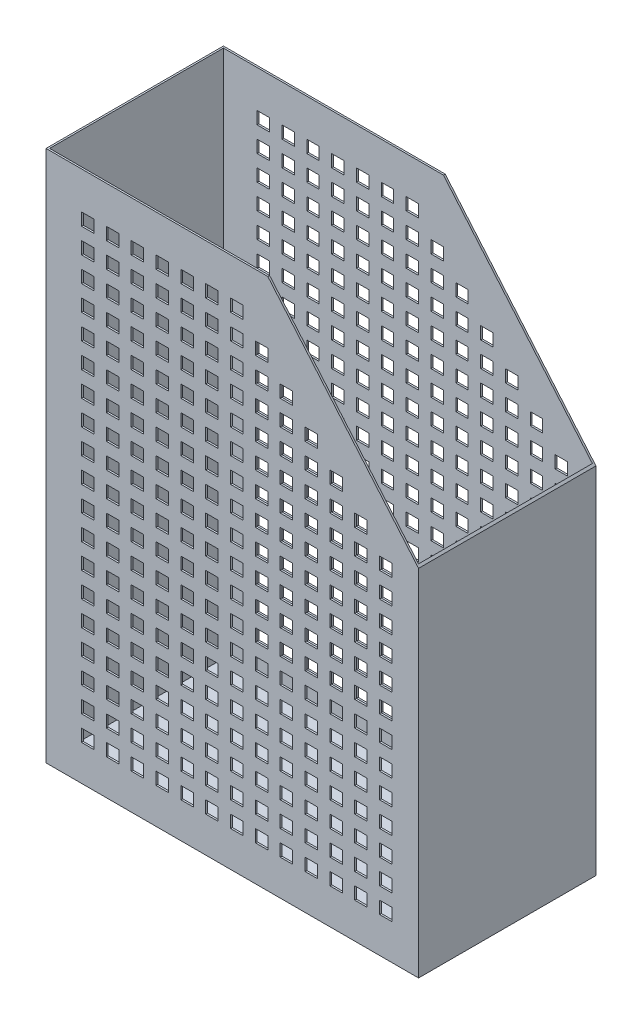
SolidWorks part; units mm, degrees
ref_plane "Front Plane" through (0, 0, 0) normal (0, 0, 1) x (1, 0, 0)
ref_plane "Top Plane" through (0, 0, 0) normal (0, 1, 0) x (1, 0, 0)
ref_plane "Right Plane" through (0, 0, 0) normal (1, 0, 0) x (0, 0, -1)
sketch "Sketch1" plane through (0, 0, 0) normal (0, 0, 1) x (1, 0, 0)
  line L0 (0, 0) -> (0, 300)
  line L1 (0, 300) -> (125, 300)
  line L2 (125, 300) -> (210, 200)
  line L3 (210, 200) -> (210, 0)
  line L4 (210, 0) -> (0, 0)
  dimension "D1" = 300
  dimension "D2" = 210
  dimension "D3" = 125
  dimension "D4" = 200
extrude "Boss-Extrude1" add sketch "Sketch1" along normal mid plane 100
shell "Shell1" thickness 1
sketch "Sketch2" plane through (0, 0, 50) normal (0, 0, 1) x (1, 0, 0)
  line L0 (0, 0) -> (210, 0) construction
  line L1 (20, 20) -> (27, 20)
  line L2 (20, 20) -> (20, 27)
  line L3 (20, 27) -> (27, 27)
  line L4 (27, 20) -> (27, 27)
  line L5 (34, 20) -> (34, 27)
  line L6 (34, 20) -> (41, 20)
  line L7 (41, 20) -> (41, 27)
  line L8 (34, 27) -> (41, 27)
  line L9 (48, 20) -> (48, 27)
  line L10 (0, 0) -> (210, 0)
  line L11 (210, 0) -> (210, 200)
  line L12 (210, 200) -> (125, 300)
  line L13 (125, 300) -> (0, 300)
  line L14 (0, 300) -> (0, 0)
  line L15 (0, 0) -> (210, 0)
  line L16 (210, 0) -> (210, 200)
  line L17 (210, 200) -> (125, 300)
  line L18 (125, 300) -> (0, 300)
  line L19 (0, 300) -> (0, 0)
  line L20 (48, 20) -> (55, 20)
  line L21 (55, 20) -> (55, 27)
  line L22 (48, 27) -> (55, 27)
  line L23 (62, 20) -> (62, 27)
  line L24 (62, 20) -> (69, 20)
  line L25 (69, 20) -> (69, 27)
  line L26 (62, 27) -> (69, 27)
  line L27 (76, 20) -> (76, 27)
  line L28 (76, 20) -> (83, 20)
  line L29 (83, 20) -> (83, 27)
  line L30 (76, 27) -> (83, 27)
  line L31 (90, 20) -> (90, 27)
  line L32 (90, 20) -> (97, 20)
  line L33 (97, 20) -> (97, 27)
  line L34 (90, 27) -> (97, 27)
  line L35 (104, 20) -> (104, 27)
  line L36 (104, 20) -> (111, 20)
  line L37 (111, 20) -> (111, 27)
  line L38 (104, 27) -> (111, 27)
  line L39 (118, 20) -> (118, 27)
  line L40 (118, 20) -> (125, 20)
  line L41 (125, 20) -> (125, 27)
  line L42 (118, 27) -> (125, 27)
  line L43 (132, 20) -> (132, 27)
  line L44 (132, 20) -> (139, 20)
  line L45 (139, 20) -> (139, 27)
  line L46 (132, 27) -> (139, 27)
  line L47 (146, 20) -> (146, 27)
  line L48 (146, 20) -> (153, 20)
  line L49 (153, 20) -> (153, 27)
  line L50 (146, 27) -> (153, 27)
  line L51 (160, 20) -> (160, 27)
  line L52 (160, 20) -> (167, 20)
  line L53 (167, 20) -> (167, 27)
  line L54 (160, 27) -> (167, 27)
  line L55 (174, 20) -> (174, 27)
  line L56 (174, 20) -> (181, 20)
  line L57 (181, 20) -> (181, 27)
  line L58 (174, 27) -> (181, 27)
  line L59 (188, 20) -> (188, 27)
  line L60 (188, 20) -> (195, 20)
  line L61 (195, 20) -> (195, 27)
  line L62 (188, 27) -> (195, 27)
  line L63 (34, 34) -> (34, 41)
  line L64 (34, 34) -> (41, 34)
  line L65 (41, 34) -> (41, 41)
  line L66 (34, 41) -> (41, 41)
  line L67 (48, 34) -> (48, 41)
  line L68 (48, 34) -> (55, 34)
  line L69 (55, 34) -> (55, 41)
  line L70 (48, 41) -> (55, 41)
  line L71 (62, 34) -> (62, 41)
  line L72 (62, 34) -> (69, 34)
  line L73 (69, 34) -> (69, 41)
  line L74 (62, 41) -> (69, 41)
  line L75 (76, 34) -> (76, 41)
  line L76 (76, 34) -> (83, 34)
  line L77 (83, 34) -> (83, 41)
  line L78 (76, 41) -> (83, 41)
  line L79 (90, 34) -> (90, 41)
  line L80 (90, 34) -> (97, 34)
  line L81 (97, 34) -> (97, 41)
  line L82 (90, 41) -> (97, 41)
  line L83 (104, 34) -> (104, 41)
  line L84 (104, 34) -> (111, 34)
  line L85 (111, 34) -> (111, 41)
  line L86 (104, 41) -> (111, 41)
  line L87 (118, 34) -> (118, 41)
  line L88 (118, 34) -> (125, 34)
  line L89 (125, 34) -> (125, 41)
  line L90 (118, 41) -> (125, 41)
  line L91 (132, 34) -> (132, 41)
  line L92 (132, 34) -> (139, 34)
  line L93 (139, 34) -> (139, 41)
  line L94 (132, 41) -> (139, 41)
  line L95 (146, 34) -> (146, 41)
  line L96 (146, 34) -> (153, 34)
  line L97 (153, 34) -> (153, 41)
  line L98 (146, 41) -> (153, 41)
  line L99 (160, 34) -> (160, 41)
  line L100 (160, 34) -> (167, 34)
  line L101 (167, 34) -> (167, 41)
  line L102 (160, 41) -> (167, 41)
  line L103 (174, 34) -> (174, 41)
  line L104 (174, 34) -> (181, 34)
  line L105 (181, 34) -> (181, 41)
  line L106 (174, 41) -> (181, 41)
  line L107 (188, 34) -> (188, 41)
  line L108 (188, 34) -> (195, 34)
  line L109 (195, 34) -> (195, 41)
  line L110 (188, 41) -> (195, 41)
  line L111 (34, 48) -> (34, 55)
  line L112 (34, 48) -> (41, 48)
  line L113 (41, 48) -> (41, 55)
  line L114 (34, 55) -> (41, 55)
  line L115 (48, 48) -> (48, 55)
  line L116 (48, 48) -> (55, 48)
  line L117 (55, 48) -> (55, 55)
  line L118 (48, 55) -> (55, 55)
  line L119 (62, 48) -> (62, 55)
  line L120 (62, 48) -> (69, 48)
  line L121 (69, 48) -> (69, 55)
  line L122 (62, 55) -> (69, 55)
  line L123 (76, 48) -> (76, 55)
  line L124 (76, 48) -> (83, 48)
  line L125 (83, 48) -> (83, 55)
  line L126 (76, 55) -> (83, 55)
  line L127 (90, 48) -> (90, 55)
  line L128 (90, 48) -> (97, 48)
  line L129 (97, 48) -> (97, 55)
  line L130 (90, 55) -> (97, 55)
  line L131 (104, 48) -> (104, 55)
  line L132 (104, 48) -> (111, 48)
  line L133 (111, 48) -> (111, 55)
  line L134 (104, 55) -> (111, 55)
  line L135 (118, 48) -> (118, 55)
  line L136 (118, 48) -> (125, 48)
  line L137 (125, 48) -> (125, 55)
  line L138 (118, 55) -> (125, 55)
  line L139 (132, 48) -> (132, 55)
  line L140 (132, 48) -> (139, 48)
  line L141 (139, 48) -> (139, 55)
  line L142 (132, 55) -> (139, 55)
  line L143 (146, 48) -> (146, 55)
  line L144 (146, 48) -> (153, 48)
  line L145 (153, 48) -> (153, 55)
  line L146 (146, 55) -> (153, 55)
  line L147 (160, 48) -> (160, 55)
  line L148 (160, 48) -> (167, 48)
  line L149 (167, 48) -> (167, 55)
  line L150 (160, 55) -> (167, 55)
  line L151 (174, 48) -> (174, 55)
  line L152 (174, 48) -> (181, 48)
  line L153 (181, 48) -> (181, 55)
  line L154 (174, 55) -> (181, 55)
  line L155 (188, 48) -> (188, 55)
  line L156 (188, 48) -> (195, 48)
  line L157 (195, 48) -> (195, 55)
  line L158 (188, 55) -> (195, 55)
  line L159 (34, 62) -> (34, 69)
  line L160 (34, 62) -> (41, 62)
  line L161 (41, 62) -> (41, 69)
  line L162 (34, 69) -> (41, 69)
  line L163 (48, 62) -> (48, 69)
  line L164 (48, 62) -> (55, 62)
  line L165 (55, 62) -> (55, 69)
  line L166 (48, 69) -> (55, 69)
  line L167 (62, 62) -> (62, 69)
  line L168 (62, 62) -> (69, 62)
  line L169 (69, 62) -> (69, 69)
  line L170 (62, 69) -> (69, 69)
  line L171 (76, 62) -> (76, 69)
  line L172 (76, 62) -> (83, 62)
  line L173 (83, 62) -> (83, 69)
  line L174 (76, 69) -> (83, 69)
  line L175 (90, 62) -> (90, 69)
  line L176 (90, 62) -> (97, 62)
  line L177 (97, 62) -> (97, 69)
  line L178 (90, 69) -> (97, 69)
  line L179 (104, 62) -> (104, 69)
  line L180 (104, 62) -> (111, 62)
  line L181 (111, 62) -> (111, 69)
  line L182 (104, 69) -> (111, 69)
  line L183 (118, 62) -> (118, 69)
  line L184 (118, 62) -> (125, 62)
  line L185 (125, 62) -> (125, 69)
  line L186 (118, 69) -> (125, 69)
  line L187 (132, 62) -> (132, 69)
  line L188 (132, 62) -> (139, 62)
  line L189 (139, 62) -> (139, 69)
  line L190 (132, 69) -> (139, 69)
  line L191 (146, 62) -> (146, 69)
  line L192 (146, 62) -> (153, 62)
  line L193 (153, 62) -> (153, 69)
  line L194 (146, 69) -> (153, 69)
  line L195 (160, 62) -> (160, 69)
  line L196 (160, 62) -> (167, 62)
  line L197 (167, 62) -> (167, 69)
  line L198 (160, 69) -> (167, 69)
  line L199 (174, 62) -> (174, 69)
  line L200 (174, 62) -> (181, 62)
  line L201 (181, 62) -> (181, 69)
  line L202 (174, 69) -> (181, 69)
  line L203 (188, 62) -> (188, 69)
  line L204 (188, 62) -> (195, 62)
  line L205 (195, 62) -> (195, 69)
  line L206 (188, 69) -> (195, 69)
  line L207 (34, 76) -> (34, 83)
  line L208 (34, 76) -> (41, 76)
  line L209 (41, 76) -> (41, 83)
  line L210 (34, 83) -> (41, 83)
  line L211 (48, 76) -> (48, 83)
  line L212 (48, 76) -> (55, 76)
  line L213 (55, 76) -> (55, 83)
  line L214 (48, 83) -> (55, 83)
  line L215 (62, 76) -> (62, 83)
  line L216 (62, 76) -> (69, 76)
  line L217 (69, 76) -> (69, 83)
  line L218 (62, 83) -> (69, 83)
  line L219 (76, 76) -> (76, 83)
  line L220 (76, 76) -> (83, 76)
  line L221 (83, 76) -> (83, 83)
  line L222 (76, 83) -> (83, 83)
  line L223 (90, 76) -> (90, 83)
  line L224 (90, 76) -> (97, 76)
  line L225 (97, 76) -> (97, 83)
  line L226 (90, 83) -> (97, 83)
  line L227 (104, 76) -> (104, 83)
  line L228 (104, 76) -> (111, 76)
  line L229 (111, 76) -> (111, 83)
  line L230 (104, 83) -> (111, 83)
  line L231 (118, 76) -> (118, 83)
  line L232 (118, 76) -> (125, 76)
  line L233 (125, 76) -> (125, 83)
  line L234 (118, 83) -> (125, 83)
  line L235 (132, 76) -> (132, 83)
  line L236 (132, 76) -> (139, 76)
  line L237 (139, 76) -> (139, 83)
  line L238 (132, 83) -> (139, 83)
  line L239 (146, 76) -> (146, 83)
  line L240 (146, 76) -> (153, 76)
  line L241 (153, 76) -> (153, 83)
  line L242 (146, 83) -> (153, 83)
  line L243 (160, 76) -> (160, 83)
  line L244 (160, 76) -> (167, 76)
  line L245 (167, 76) -> (167, 83)
  line L246 (160, 83) -> (167, 83)
  line L247 (174, 76) -> (174, 83)
  line L248 (174, 76) -> (181, 76)
  line L249 (181, 76) -> (181, 83)
  line L250 (174, 83) -> (181, 83)
  line L251 (188, 76) -> (188, 83)
  line L252 (188, 76) -> (195, 76)
  line L253 (195, 76) -> (195, 83)
  line L254 (188, 83) -> (195, 83)
  line L255 (34, 90) -> (34, 97)
  line L256 (34, 90) -> (41, 90)
  line L257 (41, 90) -> (41, 97)
  line L258 (34, 97) -> (41, 97)
  line L259 (48, 90) -> (48, 97)
  line L260 (48, 90) -> (55, 90)
  line L261 (55, 90) -> (55, 97)
  line L262 (48, 97) -> (55, 97)
  line L263 (62, 90) -> (62, 97)
  line L264 (62, 90) -> (69, 90)
  line L265 (69, 90) -> (69, 97)
  line L266 (62, 97) -> (69, 97)
  line L267 (76, 90) -> (76, 97)
  line L268 (76, 90) -> (83, 90)
  line L269 (83, 90) -> (83, 97)
  line L270 (76, 97) -> (83, 97)
  line L271 (90, 90) -> (90, 97)
  line L272 (90, 90) -> (97, 90)
  line L273 (97, 90) -> (97, 97)
  line L274 (90, 97) -> (97, 97)
  line L275 (104, 90) -> (104, 97)
  line L276 (104, 90) -> (111, 90)
  line L277 (111, 90) -> (111, 97)
  line L278 (104, 97) -> (111, 97)
  line L279 (118, 90) -> (118, 97)
  line L280 (118, 90) -> (125, 90)
  line L281 (125, 90) -> (125, 97)
  line L282 (118, 97) -> (125, 97)
  line L283 (132, 90) -> (132, 97)
  line L284 (132, 90) -> (139, 90)
  line L285 (139, 90) -> (139, 97)
  line L286 (132, 97) -> (139, 97)
  line L287 (146, 90) -> (146, 97)
  line L288 (146, 90) -> (153, 90)
  line L289 (153, 90) -> (153, 97)
  line L290 (146, 97) -> (153, 97)
  line L291 (160, 90) -> (160, 97)
  line L292 (160, 90) -> (167, 90)
  line L293 (167, 90) -> (167, 97)
  line L294 (160, 97) -> (167, 97)
  line L295 (174, 90) -> (174, 97)
  line L296 (174, 90) -> (181, 90)
  line L297 (181, 90) -> (181, 97)
  line L298 (174, 97) -> (181, 97)
  line L299 (188, 90) -> (188, 97)
  line L300 (188, 90) -> (195, 90)
  line L301 (195, 90) -> (195, 97)
  line L302 (188, 97) -> (195, 97)
  line L303 (34, 104) -> (34, 111)
  line L304 (34, 104) -> (41, 104)
  line L305 (41, 104) -> (41, 111)
  line L306 (34, 111) -> (41, 111)
  line L307 (48, 104) -> (48, 111)
  line L308 (48, 104) -> (55, 104)
  line L309 (55, 104) -> (55, 111)
  line L310 (48, 111) -> (55, 111)
  line L311 (62, 104) -> (62, 111)
  line L312 (62, 104) -> (69, 104)
  line L313 (69, 104) -> (69, 111)
  line L314 (62, 111) -> (69, 111)
  line L315 (76, 104) -> (76, 111)
  line L316 (76, 104) -> (83, 104)
  line L317 (83, 104) -> (83, 111)
  line L318 (76, 111) -> (83, 111)
  line L319 (90, 104) -> (90, 111)
  line L320 (90, 104) -> (97, 104)
  line L321 (97, 104) -> (97, 111)
  line L322 (90, 111) -> (97, 111)
  line L323 (104, 104) -> (104, 111)
  line L324 (104, 104) -> (111, 104)
  line L325 (111, 104) -> (111, 111)
  line L326 (104, 111) -> (111, 111)
  line L327 (118, 104) -> (118, 111)
  line L328 (118, 104) -> (125, 104)
  line L329 (125, 104) -> (125, 111)
  line L330 (118, 111) -> (125, 111)
  line L331 (132, 104) -> (132, 111)
  line L332 (132, 104) -> (139, 104)
  line L333 (139, 104) -> (139, 111)
  line L334 (132, 111) -> (139, 111)
  line L335 (146, 104) -> (146, 111)
  line L336 (146, 104) -> (153, 104)
  line L337 (153, 104) -> (153, 111)
  line L338 (146, 111) -> (153, 111)
  line L339 (160, 104) -> (160, 111)
  line L340 (160, 104) -> (167, 104)
  line L341 (167, 104) -> (167, 111)
  line L342 (160, 111) -> (167, 111)
  line L343 (174, 104) -> (174, 111)
  line L344 (174, 104) -> (181, 104)
  line L345 (181, 104) -> (181, 111)
  line L346 (174, 111) -> (181, 111)
  line L347 (188, 104) -> (188, 111)
  line L348 (188, 104) -> (195, 104)
  line L349 (195, 104) -> (195, 111)
  line L350 (188, 111) -> (195, 111)
  line L351 (34, 118) -> (34, 125)
  line L352 (34, 118) -> (41, 118)
  line L353 (41, 118) -> (41, 125)
  line L354 (34, 125) -> (41, 125)
  line L355 (48, 118) -> (48, 125)
  line L356 (48, 118) -> (55, 118)
  line L357 (55, 118) -> (55, 125)
  line L358 (48, 125) -> (55, 125)
  line L359 (62, 118) -> (62, 125)
  line L360 (62, 118) -> (69, 118)
  line L361 (69, 118) -> (69, 125)
  line L362 (62, 125) -> (69, 125)
  line L363 (76, 118) -> (76, 125)
  line L364 (76, 118) -> (83, 118)
  line L365 (83, 118) -> (83, 125)
  line L366 (76, 125) -> (83, 125)
  line L367 (90, 118) -> (90, 125)
  line L368 (90, 118) -> (97, 118)
  line L369 (97, 118) -> (97, 125)
  line L370 (90, 125) -> (97, 125)
  line L371 (104, 118) -> (104, 125)
  line L372 (104, 118) -> (111, 118)
  line L373 (111, 118) -> (111, 125)
  line L374 (104, 125) -> (111, 125)
  line L375 (118, 118) -> (118, 125)
  line L376 (118, 118) -> (125, 118)
  line L377 (125, 118) -> (125, 125)
  line L378 (118, 125) -> (125, 125)
  line L379 (132, 118) -> (132, 125)
  line L380 (132, 118) -> (139, 118)
  line L381 (139, 118) -> (139, 125)
  line L382 (132, 125) -> (139, 125)
  line L383 (146, 118) -> (146, 125)
  line L384 (146, 118) -> (153, 118)
  line L385 (153, 118) -> (153, 125)
  line L386 (146, 125) -> (153, 125)
  line L387 (160, 118) -> (160, 125)
  line L388 (160, 118) -> (167, 118)
  line L389 (167, 118) -> (167, 125)
  line L390 (160, 125) -> (167, 125)
  line L391 (174, 118) -> (174, 125)
  line L392 (174, 118) -> (181, 118)
  line L393 (181, 118) -> (181, 125)
  line L394 (174, 125) -> (181, 125)
  line L395 (188, 118) -> (188, 125)
  line L396 (188, 118) -> (195, 118)
  line L397 (195, 118) -> (195, 125)
  line L398 (188, 125) -> (195, 125)
  line L399 (34, 132) -> (34, 139)
  line L400 (34, 132) -> (41, 132)
  line L401 (41, 132) -> (41, 139)
  line L402 (34, 139) -> (41, 139)
  line L403 (48, 132) -> (48, 139)
  line L404 (48, 132) -> (55, 132)
  line L405 (55, 132) -> (55, 139)
  line L406 (48, 139) -> (55, 139)
  line L407 (62, 132) -> (62, 139)
  line L408 (62, 132) -> (69, 132)
  line L409 (69, 132) -> (69, 139)
  line L410 (62, 139) -> (69, 139)
  line L411 (76, 132) -> (76, 139)
  line L412 (76, 132) -> (83, 132)
  line L413 (83, 132) -> (83, 139)
  line L414 (76, 139) -> (83, 139)
  line L415 (90, 132) -> (90, 139)
  line L416 (90, 132) -> (97, 132)
  line L417 (97, 132) -> (97, 139)
  line L418 (90, 139) -> (97, 139)
  line L419 (104, 132) -> (104, 139)
  line L420 (104, 132) -> (111, 132)
  line L421 (111, 132) -> (111, 139)
  line L422 (104, 139) -> (111, 139)
  line L423 (118, 132) -> (118, 139)
  line L424 (118, 132) -> (125, 132)
  line L425 (125, 132) -> (125, 139)
  line L426 (118, 139) -> (125, 139)
  line L427 (132, 132) -> (132, 139)
  line L428 (132, 132) -> (139, 132)
  line L429 (139, 132) -> (139, 139)
  line L430 (132, 139) -> (139, 139)
  line L431 (146, 132) -> (146, 139)
  line L432 (146, 132) -> (153, 132)
  line L433 (153, 132) -> (153, 139)
  line L434 (146, 139) -> (153, 139)
  line L435 (160, 132) -> (160, 139)
  line L436 (160, 132) -> (167, 132)
  line L437 (167, 132) -> (167, 139)
  line L438 (160, 139) -> (167, 139)
  line L439 (174, 132) -> (174, 139)
  line L440 (174, 132) -> (181, 132)
  line L441 (181, 132) -> (181, 139)
  line L442 (174, 139) -> (181, 139)
  line L443 (188, 132) -> (188, 139)
  line L444 (188, 132) -> (195, 132)
  line L445 (195, 132) -> (195, 139)
  line L446 (188, 139) -> (195, 139)
  line L447 (34, 146) -> (34, 153)
  line L448 (34, 146) -> (41, 146)
  line L449 (41, 146) -> (41, 153)
  line L450 (34, 153) -> (41, 153)
  line L451 (48, 146) -> (48, 153)
  line L452 (48, 146) -> (55, 146)
  line L453 (55, 146) -> (55, 153)
  line L454 (48, 153) -> (55, 153)
  line L455 (62, 146) -> (62, 153)
  line L456 (62, 146) -> (69, 146)
  line L457 (69, 146) -> (69, 153)
  line L458 (62, 153) -> (69, 153)
  line L459 (76, 146) -> (76, 153)
  line L460 (76, 146) -> (83, 146)
  line L461 (83, 146) -> (83, 153)
  line L462 (76, 153) -> (83, 153)
  line L463 (90, 146) -> (90, 153)
  line L464 (90, 146) -> (97, 146)
  line L465 (97, 146) -> (97, 153)
  line L466 (90, 153) -> (97, 153)
  line L467 (104, 146) -> (104, 153)
  line L468 (104, 146) -> (111, 146)
  line L469 (111, 146) -> (111, 153)
  line L470 (104, 153) -> (111, 153)
  line L471 (118, 146) -> (118, 153)
  line L472 (118, 146) -> (125, 146)
  line L473 (125, 146) -> (125, 153)
  line L474 (118, 153) -> (125, 153)
  line L475 (132, 146) -> (132, 153)
  line L476 (132, 146) -> (139, 146)
  line L477 (139, 146) -> (139, 153)
  line L478 (132, 153) -> (139, 153)
  line L479 (146, 146) -> (146, 153)
  line L480 (146, 146) -> (153, 146)
  line L481 (153, 146) -> (153, 153)
  line L482 (146, 153) -> (153, 153)
  line L483 (160, 146) -> (160, 153)
  line L484 (160, 146) -> (167, 146)
  line L485 (167, 146) -> (167, 153)
  line L486 (160, 153) -> (167, 153)
  line L487 (174, 146) -> (174, 153)
  line L488 (174, 146) -> (181, 146)
  line L489 (181, 146) -> (181, 153)
  line L490 (174, 153) -> (181, 153)
  line L491 (188, 146) -> (188, 153)
  line L492 (188, 146) -> (195, 146)
  line L493 (195, 146) -> (195, 153)
  line L494 (188, 153) -> (195, 153)
  line L495 (34, 160) -> (34, 167)
  line L496 (34, 160) -> (41, 160)
  line L497 (41, 160) -> (41, 167)
  line L498 (34, 167) -> (41, 167)
  line L499 (48, 160) -> (48, 167)
  line L500 (48, 160) -> (55, 160)
  line L501 (55, 160) -> (55, 167)
  line L502 (48, 167) -> (55, 167)
  line L503 (62, 160) -> (62, 167)
  line L504 (62, 160) -> (69, 160)
  line L505 (69, 160) -> (69, 167)
  line L506 (62, 167) -> (69, 167)
  line L507 (76, 160) -> (76, 167)
  line L508 (76, 160) -> (83, 160)
  line L509 (83, 160) -> (83, 167)
  line L510 (76, 167) -> (83, 167)
  line L511 (90, 160) -> (90, 167)
  line L512 (90, 160) -> (97, 160)
  line L513 (97, 160) -> (97, 167)
  line L514 (90, 167) -> (97, 167)
  line L515 (104, 160) -> (104, 167)
  line L516 (104, 160) -> (111, 160)
  line L517 (111, 160) -> (111, 167)
  line L518 (104, 167) -> (111, 167)
  line L519 (118, 160) -> (118, 167)
  line L520 (118, 160) -> (125, 160)
  line L521 (125, 160) -> (125, 167)
  line L522 (118, 167) -> (125, 167)
  line L523 (132, 160) -> (132, 167)
  line L524 (132, 160) -> (139, 160)
  line L525 (139, 160) -> (139, 167)
  line L526 (132, 167) -> (139, 167)
  line L527 (146, 160) -> (146, 167)
  line L528 (146, 160) -> (153, 160)
  line L529 (153, 160) -> (153, 167)
  line L530 (146, 167) -> (153, 167)
  line L531 (160, 160) -> (160, 167)
  line L532 (160, 160) -> (167, 160)
  line L533 (167, 160) -> (167, 167)
  line L534 (160, 167) -> (167, 167)
  line L535 (174, 160) -> (174, 167)
  line L536 (174, 160) -> (181, 160)
  line L537 (181, 160) -> (181, 167)
  line L538 (174, 167) -> (181, 167)
  line L539 (188, 160) -> (188, 167)
  line L540 (188, 160) -> (195, 160)
  line L541 (195, 160) -> (195, 167)
  line L542 (188, 167) -> (195, 167)
  line L543 (34, 174) -> (34, 181)
  line L544 (34, 174) -> (41, 174)
  line L545 (41, 174) -> (41, 181)
  line L546 (34, 181) -> (41, 181)
  line L547 (48, 174) -> (48, 181)
  line L548 (48, 174) -> (55, 174)
  line L549 (55, 174) -> (55, 181)
  line L550 (48, 181) -> (55, 181)
  line L551 (62, 174) -> (62, 181)
  line L552 (62, 174) -> (69, 174)
  line L553 (69, 174) -> (69, 181)
  line L554 (62, 181) -> (69, 181)
  line L555 (76, 174) -> (76, 181)
  line L556 (76, 174) -> (83, 174)
  line L557 (83, 174) -> (83, 181)
  line L558 (76, 181) -> (83, 181)
  line L559 (90, 174) -> (90, 181)
  line L560 (90, 174) -> (97, 174)
  line L561 (97, 174) -> (97, 181)
  line L562 (90, 181) -> (97, 181)
  line L563 (104, 174) -> (104, 181)
  line L564 (104, 174) -> (111, 174)
  line L565 (111, 174) -> (111, 181)
  line L566 (104, 181) -> (111, 181)
  line L567 (118, 174) -> (118, 181)
  line L568 (118, 174) -> (125, 174)
  line L569 (125, 174) -> (125, 181)
  line L570 (118, 181) -> (125, 181)
  line L571 (132, 174) -> (132, 181)
  line L572 (132, 174) -> (139, 174)
  line L573 (139, 174) -> (139, 181)
  line L574 (132, 181) -> (139, 181)
  line L575 (146, 174) -> (146, 181)
  line L576 (146, 174) -> (153, 174)
  line L577 (153, 174) -> (153, 181)
  line L578 (146, 181) -> (153, 181)
  line L579 (160, 174) -> (160, 181)
  line L580 (160, 174) -> (167, 174)
  line L581 (167, 174) -> (167, 181)
  line L582 (160, 181) -> (167, 181)
  line L583 (174, 174) -> (174, 181)
  line L584 (174, 174) -> (181, 174)
  line L585 (181, 174) -> (181, 181)
  line L586 (174, 181) -> (181, 181)
  line L587 (188, 174) -> (188, 181)
  line L588 (188, 174) -> (195, 174)
  line L589 (195, 174) -> (195, 181)
  line L590 (188, 181) -> (195, 181)
  line L591 (34, 188) -> (34, 195)
  line L592 (34, 188) -> (41, 188)
  line L593 (41, 188) -> (41, 195)
  line L594 (34, 195) -> (41, 195)
  line L595 (48, 188) -> (48, 195)
  line L596 (48, 188) -> (55, 188)
  line L597 (55, 188) -> (55, 195)
  line L598 (48, 195) -> (55, 195)
  line L599 (62, 188) -> (62, 195)
  line L600 (62, 188) -> (69, 188)
  line L601 (69, 188) -> (69, 195)
  line L602 (62, 195) -> (69, 195)
  line L603 (76, 188) -> (76, 195)
  line L604 (76, 188) -> (83, 188)
  line L605 (83, 188) -> (83, 195)
  line L606 (76, 195) -> (83, 195)
  line L607 (90, 188) -> (90, 195)
  line L608 (90, 188) -> (97, 188)
  line L609 (97, 188) -> (97, 195)
  line L610 (90, 195) -> (97, 195)
  line L611 (104, 188) -> (104, 195)
  line L612 (104, 188) -> (111, 188)
  line L613 (111, 188) -> (111, 195)
  line L614 (104, 195) -> (111, 195)
  line L615 (118, 188) -> (118, 195)
  line L616 (118, 188) -> (125, 188)
  line L617 (125, 188) -> (125, 195)
  line L618 (118, 195) -> (125, 195)
  line L619 (132, 188) -> (132, 195)
  line L620 (132, 188) -> (139, 188)
  line L621 (139, 188) -> (139, 195)
  line L622 (132, 195) -> (139, 195)
  line L623 (146, 188) -> (146, 195)
  line L624 (146, 188) -> (153, 188)
  line L625 (153, 188) -> (153, 195)
  line L626 (146, 195) -> (153, 195)
  line L627 (160, 188) -> (160, 195)
  line L628 (160, 188) -> (167, 188)
  line L629 (167, 188) -> (167, 195)
  line L630 (160, 195) -> (167, 195)
  line L631 (174, 188) -> (174, 195)
  line L632 (174, 188) -> (181, 188)
  line L633 (181, 188) -> (181, 195)
  line L634 (174, 195) -> (181, 195)
  line L635 (188, 188) -> (188, 195)
  line L636 (188, 188) -> (195, 188)
  line L637 (195, 188) -> (195, 195)
  line L638 (188, 195) -> (195, 195)
  line L639 (34, 202) -> (34, 209)
  line L640 (34, 202) -> (41, 202)
  line L641 (41, 202) -> (41, 209)
  line L642 (34, 209) -> (41, 209)
  line L643 (48, 202) -> (48, 209)
  line L644 (48, 202) -> (55, 202)
  line L645 (55, 202) -> (55, 209)
  line L646 (48, 209) -> (55, 209)
  line L647 (62, 202) -> (62, 209)
  line L648 (62, 202) -> (69, 202)
  line L649 (69, 202) -> (69, 209)
  line L650 (62, 209) -> (69, 209)
  line L651 (76, 202) -> (76, 209)
  line L652 (76, 202) -> (83, 202)
  line L653 (83, 202) -> (83, 209)
  line L654 (76, 209) -> (83, 209)
  line L655 (90, 202) -> (90, 209)
  line L656 (90, 202) -> (97, 202)
  line L657 (97, 202) -> (97, 209)
  line L658 (90, 209) -> (97, 209)
  line L659 (104, 202) -> (104, 209)
  line L660 (104, 202) -> (111, 202)
  line L661 (111, 202) -> (111, 209)
  line L662 (104, 209) -> (111, 209)
  line L663 (118, 202) -> (118, 209)
  line L664 (118, 202) -> (125, 202)
  line L665 (125, 202) -> (125, 209)
  line L666 (118, 209) -> (125, 209)
  line L667 (132, 202) -> (132, 209)
  line L668 (132, 202) -> (139, 202)
  line L669 (139, 202) -> (139, 209)
  line L670 (132, 209) -> (139, 209)
  line L671 (146, 202) -> (146, 209)
  line L672 (146, 202) -> (153, 202)
  line L673 (153, 202) -> (153, 209)
  line L674 (146, 209) -> (153, 209)
  line L675 (160, 202) -> (160, 209)
  line L676 (160, 202) -> (167, 202)
  line L677 (167, 202) -> (167, 209)
  line L678 (160, 209) -> (167, 209)
  line L679 (174, 202) -> (174, 209)
  line L680 (174, 202) -> (181, 202)
  line L681 (181, 202) -> (181, 209)
  line L682 (174, 209) -> (181, 209)
  line L683 (188, 202) -> (188, 209) [skipped]
  line L684 (188, 202) -> (195, 202) [skipped]
  line L685 (195, 202) -> (195, 209) [skipped]
  line L686 (188, 209) -> (195, 209) [skipped]
  line L687 (34, 216) -> (34, 223)
  line L688 (34, 216) -> (41, 216)
  line L689 (41, 216) -> (41, 223)
  line L690 (34, 223) -> (41, 223)
  line L691 (48, 216) -> (48, 223)
  line L692 (48, 216) -> (55, 216)
  line L693 (55, 216) -> (55, 223)
  line L694 (48, 223) -> (55, 223)
  line L695 (62, 216) -> (62, 223)
  line L696 (62, 216) -> (69, 216)
  line L697 (69, 216) -> (69, 223)
  line L698 (62, 223) -> (69, 223)
  line L699 (76, 216) -> (76, 223)
  line L700 (76, 216) -> (83, 216)
  line L701 (83, 216) -> (83, 223)
  line L702 (76, 223) -> (83, 223)
  line L703 (90, 216) -> (90, 223)
  line L704 (90, 216) -> (97, 216)
  line L705 (97, 216) -> (97, 223)
  line L706 (90, 223) -> (97, 223)
  line L707 (104, 216) -> (104, 223)
  line L708 (104, 216) -> (111, 216)
  line L709 (111, 216) -> (111, 223)
  line L710 (104, 223) -> (111, 223)
  line L711 (118, 216) -> (118, 223)
  line L712 (118, 216) -> (125, 216)
  line L713 (125, 216) -> (125, 223)
  line L714 (118, 223) -> (125, 223)
  line L715 (132, 216) -> (132, 223)
  line L716 (132, 216) -> (139, 216)
  line L717 (139, 216) -> (139, 223)
  line L718 (132, 223) -> (139, 223)
  line L719 (146, 216) -> (146, 223)
  line L720 (146, 216) -> (153, 216)
  line L721 (153, 216) -> (153, 223)
  line L722 (146, 223) -> (153, 223)
  line L723 (160, 216) -> (160, 223)
  line L724 (160, 216) -> (167, 216)
  line L725 (167, 216) -> (167, 223)
  line L726 (160, 223) -> (167, 223)
  line L727 (174, 216) -> (174, 223) [skipped]
  line L728 (174, 216) -> (181, 216) [skipped]
  line L729 (181, 216) -> (181, 223) [skipped]
  line L730 (174, 223) -> (181, 223) [skipped]
  line L731 (188, 216) -> (188, 223) [skipped]
  line L732 (188, 216) -> (195, 216) [skipped]
  line L733 (195, 216) -> (195, 223) [skipped]
  line L734 (188, 223) -> (195, 223) [skipped]
  line L735 (34, 230) -> (34, 237)
  line L736 (34, 230) -> (41, 230)
  line L737 (41, 230) -> (41, 237)
  line L738 (34, 237) -> (41, 237)
  line L739 (48, 230) -> (48, 237)
  line L740 (48, 230) -> (55, 230)
  line L741 (55, 230) -> (55, 237)
  line L742 (48, 237) -> (55, 237)
  line L743 (62, 230) -> (62, 237)
  line L744 (62, 230) -> (69, 230)
  line L745 (69, 230) -> (69, 237)
  line L746 (62, 237) -> (69, 237)
  line L747 (76, 230) -> (76, 237)
  line L748 (76, 230) -> (83, 230)
  line L749 (83, 230) -> (83, 237)
  line L750 (76, 237) -> (83, 237)
  line L751 (90, 230) -> (90, 237)
  line L752 (90, 230) -> (97, 230)
  line L753 (97, 230) -> (97, 237)
  line L754 (90, 237) -> (97, 237)
  line L755 (104, 230) -> (104, 237)
  line L756 (104, 230) -> (111, 230)
  line L757 (111, 230) -> (111, 237)
  line L758 (104, 237) -> (111, 237)
  line L759 (118, 230) -> (118, 237)
  line L760 (118, 230) -> (125, 230)
  line L761 (125, 230) -> (125, 237)
  line L762 (118, 237) -> (125, 237)
  line L763 (132, 230) -> (132, 237)
  line L764 (132, 230) -> (139, 230)
  line L765 (139, 230) -> (139, 237)
  line L766 (132, 237) -> (139, 237)
  line L767 (146, 230) -> (146, 237)
  line L768 (146, 230) -> (153, 230)
  line L769 (153, 230) -> (153, 237)
  line L770 (146, 237) -> (153, 237)
  line L771 (160, 230) -> (160, 237) [skipped]
  line L772 (160, 230) -> (167, 230) [skipped]
  line L773 (167, 230) -> (167, 237) [skipped]
  line L774 (160, 237) -> (167, 237) [skipped]
  line L775 (174, 230) -> (174, 237) [skipped]
  line L776 (174, 230) -> (181, 230) [skipped]
  line L777 (181, 230) -> (181, 237) [skipped]
  line L778 (174, 237) -> (181, 237) [skipped]
  line L779 (188, 230) -> (188, 237)
  line L780 (188, 230) -> (195, 230)
  line L781 (195, 230) -> (195, 237)
  line L782 (188, 237) -> (195, 237)
  line L783 (34, 244) -> (34, 251)
  line L784 (34, 244) -> (41, 244)
  line L785 (41, 244) -> (41, 251)
  line L786 (34, 251) -> (41, 251)
  line L787 (48, 244) -> (48, 251)
  line L788 (48, 244) -> (55, 244)
  line L789 (55, 244) -> (55, 251)
  line L790 (48, 251) -> (55, 251)
  line L791 (62, 244) -> (62, 251)
  line L792 (62, 244) -> (69, 244)
  line L793 (69, 244) -> (69, 251)
  line L794 (62, 251) -> (69, 251)
  line L795 (76, 244) -> (76, 251)
  line L796 (76, 244) -> (83, 244)
  line L797 (83, 244) -> (83, 251)
  line L798 (76, 251) -> (83, 251)
  line L799 (90, 244) -> (90, 251)
  line L800 (90, 244) -> (97, 244)
  line L801 (97, 244) -> (97, 251)
  line L802 (90, 251) -> (97, 251)
  line L803 (104, 244) -> (104, 251)
  line L804 (104, 244) -> (111, 244)
  line L805 (111, 244) -> (111, 251)
  line L806 (104, 251) -> (111, 251)
  line L807 (118, 244) -> (118, 251)
  line L808 (118, 244) -> (125, 244)
  line L809 (125, 244) -> (125, 251)
  line L810 (118, 251) -> (125, 251)
  line L811 (132, 244) -> (132, 251)
  line L812 (132, 244) -> (139, 244)
  line L813 (139, 244) -> (139, 251)
  line L814 (132, 251) -> (139, 251)
  line L815 (146, 244) -> (146, 251) [skipped]
  line L816 (146, 244) -> (153, 244) [skipped]
  line L817 (153, 244) -> (153, 251) [skipped]
  line L818 (146, 251) -> (153, 251) [skipped]
  line L819 (160, 244) -> (160, 251) [skipped]
  line L820 (160, 244) -> (167, 244) [skipped]
  line L821 (167, 244) -> (167, 251) [skipped]
  line L822 (160, 251) -> (167, 251) [skipped]
  line L823 (174, 244) -> (174, 251) [skipped]
  line L824 (174, 244) -> (181, 244) [skipped]
  line L825 (181, 244) -> (181, 251) [skipped]
  line L826 (174, 251) -> (181, 251) [skipped]
  line L827 (188, 244) -> (188, 251)
  line L828 (188, 244) -> (195, 244)
  line L829 (195, 244) -> (195, 251)
  line L830 (188, 251) -> (195, 251)
  line L831 (34, 258) -> (34, 265)
  line L832 (34, 258) -> (41, 258)
  line L833 (41, 258) -> (41, 265)
  line L834 (34, 265) -> (41, 265)
  line L835 (48, 258) -> (48, 265)
  line L836 (48, 258) -> (55, 258)
  line L837 (55, 258) -> (55, 265)
  line L838 (48, 265) -> (55, 265)
  line L839 (62, 258) -> (62, 265)
  line L840 (62, 258) -> (69, 258)
  line L841 (69, 258) -> (69, 265)
  line L842 (62, 265) -> (69, 265)
  line L843 (76, 258) -> (76, 265)
  line L844 (76, 258) -> (83, 258)
  line L845 (83, 258) -> (83, 265)
  line L846 (76, 265) -> (83, 265)
  line L847 (90, 258) -> (90, 265)
  line L848 (90, 258) -> (97, 258)
  line L849 (97, 258) -> (97, 265)
  line L850 (90, 265) -> (97, 265)
  line L851 (104, 258) -> (104, 265)
  line L852 (104, 258) -> (111, 258)
  line L853 (111, 258) -> (111, 265)
  line L854 (104, 265) -> (111, 265)
  line L855 (118, 258) -> (118, 265)
  line L856 (118, 258) -> (125, 258)
  line L857 (125, 258) -> (125, 265)
  line L858 (118, 265) -> (125, 265)
  line L859 (132, 258) -> (132, 265) [skipped]
  line L860 (132, 258) -> (139, 258) [skipped]
  line L861 (139, 258) -> (139, 265) [skipped]
  line L862 (132, 265) -> (139, 265) [skipped]
  line L863 (146, 258) -> (146, 265) [skipped]
  line L864 (146, 258) -> (153, 258) [skipped]
  line L865 (153, 258) -> (153, 265) [skipped]
  line L866 (146, 265) -> (153, 265) [skipped]
  line L867 (160, 258) -> (160, 265) [skipped]
  line L868 (160, 258) -> (167, 258) [skipped]
  line L869 (167, 258) -> (167, 265) [skipped]
  line L870 (160, 265) -> (167, 265) [skipped]
  line L871 (174, 258) -> (174, 265)
  line L872 (174, 258) -> (181, 258)
  line L873 (181, 258) -> (181, 265)
  line L874 (174, 265) -> (181, 265)
  line L875 (188, 258) -> (188, 265)
  line L876 (188, 258) -> (195, 258)
  line L877 (195, 258) -> (195, 265)
  line L878 (188, 265) -> (195, 265)
  line L879 (34, 272) -> (34, 279)
  line L880 (34, 272) -> (41, 272)
  line L881 (41, 272) -> (41, 279)
  line L882 (34, 279) -> (41, 279)
  line L883 (48, 272) -> (48, 279)
  line L884 (48, 272) -> (55, 272)
  line L885 (55, 272) -> (55, 279)
  line L886 (48, 279) -> (55, 279)
  line L887 (62, 272) -> (62, 279)
  line L888 (62, 272) -> (69, 272)
  line L889 (69, 272) -> (69, 279)
  line L890 (62, 279) -> (69, 279)
  line L891 (76, 272) -> (76, 279)
  line L892 (76, 272) -> (83, 272)
  line L893 (83, 272) -> (83, 279)
  line L894 (76, 279) -> (83, 279)
  line L895 (90, 272) -> (90, 279)
  line L896 (90, 272) -> (97, 272)
  line L897 (97, 272) -> (97, 279)
  line L898 (90, 279) -> (97, 279)
  line L899 (104, 272) -> (104, 279)
  line L900 (104, 272) -> (111, 272)
  line L901 (111, 272) -> (111, 279)
  line L902 (104, 279) -> (111, 279)
  line L903 (118, 272) -> (118, 279) [skipped]
  line L904 (118, 272) -> (125, 272) [skipped]
  line L905 (125, 272) -> (125, 279) [skipped]
  line L906 (118, 279) -> (125, 279) [skipped]
  line L907 (132, 272) -> (132, 279) [skipped]
  line L908 (132, 272) -> (139, 272) [skipped]
  line L909 (139, 272) -> (139, 279) [skipped]
  line L910 (132, 279) -> (139, 279) [skipped]
  line L911 (146, 272) -> (146, 279) [skipped]
  line L912 (146, 272) -> (153, 272) [skipped]
  line L913 (153, 272) -> (153, 279) [skipped]
  line L914 (146, 279) -> (153, 279) [skipped]
  line L915 (160, 272) -> (160, 279)
  line L916 (160, 272) -> (167, 272)
  line L917 (167, 272) -> (167, 279)
  line L918 (160, 279) -> (167, 279)
  line L919 (174, 272) -> (174, 279)
  line L920 (174, 272) -> (181, 272)
  line L921 (181, 272) -> (181, 279)
  line L922 (174, 279) -> (181, 279)
  line L923 (188, 272) -> (188, 279)
  line L924 (188, 272) -> (195, 272)
  line L925 (195, 272) -> (195, 279)
  line L926 (188, 279) -> (195, 279)
  line L927 (20, 34) -> (20, 41)
  line L928 (20, 34) -> (27, 34)
  line L929 (27, 34) -> (27, 41)
  line L930 (20, 41) -> (27, 41)
  line L931 (20, 48) -> (20, 55)
  line L932 (20, 48) -> (27, 48)
  line L933 (27, 48) -> (27, 55)
  line L934 (20, 55) -> (27, 55)
  line L935 (20, 62) -> (20, 69)
  line L936 (20, 62) -> (27, 62)
  line L937 (27, 62) -> (27, 69)
  line L938 (20, 69) -> (27, 69)
  line L939 (20, 76) -> (20, 83)
  line L940 (20, 76) -> (27, 76)
  line L941 (27, 76) -> (27, 83)
  line L942 (20, 83) -> (27, 83)
  line L943 (20, 90) -> (20, 97)
  line L944 (20, 90) -> (27, 90)
  line L945 (27, 90) -> (27, 97)
  line L946 (20, 97) -> (27, 97)
  line L947 (20, 104) -> (20, 111)
  line L948 (20, 104) -> (27, 104)
  line L949 (27, 104) -> (27, 111)
  line L950 (20, 111) -> (27, 111)
  line L951 (20, 118) -> (20, 125)
  line L952 (20, 118) -> (27, 118)
  line L953 (27, 118) -> (27, 125)
  line L954 (20, 125) -> (27, 125)
  line L955 (20, 132) -> (20, 139)
  line L956 (20, 132) -> (27, 132)
  line L957 (27, 132) -> (27, 139)
  line L958 (20, 139) -> (27, 139)
  line L959 (20, 146) -> (20, 153)
  line L960 (20, 146) -> (27, 146)
  line L961 (27, 146) -> (27, 153)
  line L962 (20, 153) -> (27, 153)
  line L963 (20, 160) -> (20, 167)
  line L964 (20, 160) -> (27, 160)
  line L965 (27, 160) -> (27, 167)
  line L966 (20, 167) -> (27, 167)
  line L967 (20, 174) -> (20, 181)
  line L968 (20, 174) -> (27, 174)
  line L969 (27, 174) -> (27, 181)
  line L970 (20, 181) -> (27, 181)
  line L971 (20, 188) -> (20, 195)
  line L972 (20, 188) -> (27, 188)
  line L973 (27, 188) -> (27, 195)
  line L974 (20, 195) -> (27, 195)
  line L975 (20, 202) -> (20, 209)
  line L976 (20, 202) -> (27, 202)
  line L977 (27, 202) -> (27, 209)
  line L978 (20, 209) -> (27, 209)
  line L979 (20, 216) -> (20, 223)
  line L980 (20, 216) -> (27, 216)
  line L981 (27, 216) -> (27, 223)
  line L982 (20, 223) -> (27, 223)
  line L983 (20, 230) -> (20, 237)
  line L984 (20, 230) -> (27, 230)
  line L985 (27, 230) -> (27, 237)
  line L986 (20, 237) -> (27, 237)
  line L987 (20, 244) -> (20, 251)
  line L988 (20, 244) -> (27, 244)
  line L989 (27, 244) -> (27, 251)
  line L990 (20, 251) -> (27, 251)
  line L991 (20, 258) -> (20, 265)
  line L992 (20, 258) -> (27, 258)
  line L993 (27, 258) -> (27, 265)
  line L994 (20, 265) -> (27, 265)
  line L995 (20, 272) -> (20, 279)
  line L996 (20, 272) -> (27, 272)
  line L997 (27, 272) -> (27, 279)
  line L998 (20, 279) -> (27, 279)
  dimension "D1" = 7
  dimension "D2" = 7
  dimension "D3" = 20
  dimension "D4" = 0
  dimension "D5" = 20
  dimension "D6" = 13
  dimension "D7" = 19
extrude "Cut-Extrude2" cut sketch "Sketch2" against normal through all flip side to cut
